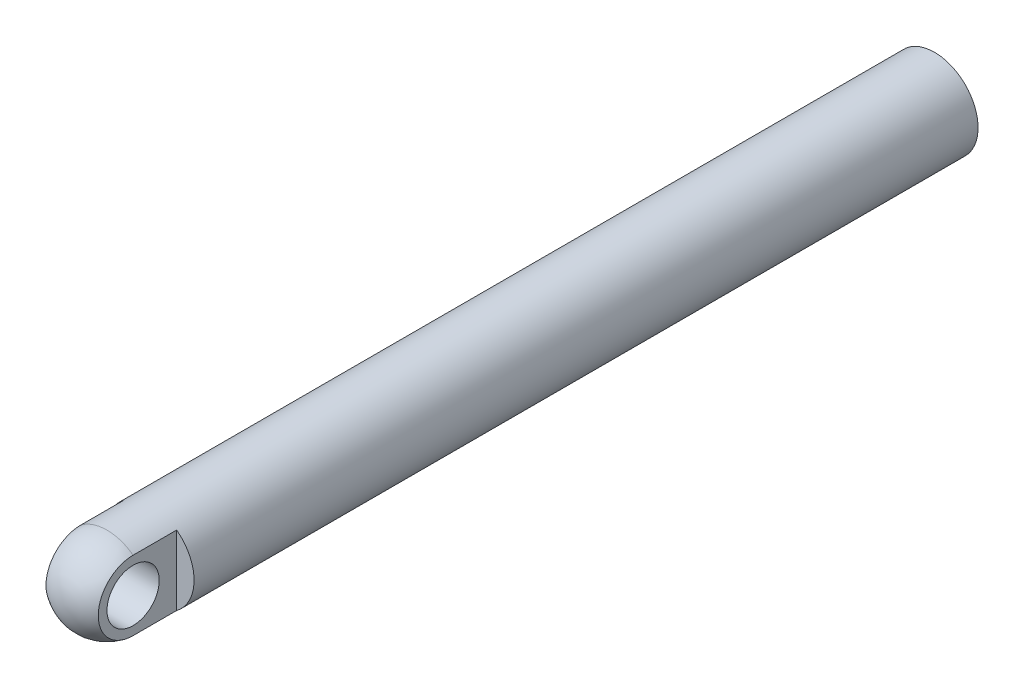
SolidWorks part; units mm, degrees
ref_plane "前视基准面" through (0, 0, 0) normal (0, 0, 1) x (1, 0, 0)
ref_plane "上视基准面" through (0, 0, 0) normal (0, 1, 0) x (1, 0, 0)
ref_plane "右视基准面" through (0, 0, 0) normal (1, 0, 0) x (0, 0, -1)
sketch "草图1" plane through (0, 0, 0) normal (0, 0, 1) x (1, 0, 0)
  circle A0 centre (0, 0) radius 50
extrude "凸台-拉伸1" add sketch "草图1" along normal blind 1150
sketch "草图2" plane through (0, 0, 1150) normal (0, 0, 1) x (1, 0, 0)
  line L1 (-30, 50) -> (-30, -50)
  line L2 (30, 50) -> (30, -50)
  line L3 (30, 50) -> (95.4457, 11.1353)
  line L4 (95.4457, 11.1353) -> (70.9724, -45.8873)
  line L5 (70.9724, -45.8873) -> (30, -50)
  line L6 (-30, -50) -> (-82.7196, -32.4271)
  line L7 (-82.7196, -32.4271) -> (-69.504, 45.1531)
  line L8 (-69.504, 45.1531) -> (-30, 50)
extrude "切除-拉伸1" cut sketch "草图2" against normal blind 100
sketch "草图3" plane through (30, 0, 0) normal (1, 0, 0) x (0, 0, -1)
  line L0 (-1050, 40) -> (-1050, -40) construction
  circle A0 centre (-1100, 0) radius 30
  dimension "D1" = 50
extrude "切除-拉伸2" cut sketch "草图3" against normal blind 100
fillet "圆角1" radius 50 1 edges at (0, 50, 1150)
sketch "草图4" plane through (0, 0, 0) normal (0, 0, -1) x (-1, 0, 0)
  circle A0 centre (0, 0) radius 50
extrude "切除-拉伸3" cut sketch "草图4" against normal blind 100
sketch "草图6" plane through (0, 0, 100) normal (0, 0, -1) x (-1, 0, 0)
  circle A0 centre (0, 0) radius 72.9064
extrude "切除-拉伸4" cut sketch "草图6" against normal blind 50
scale "缩放比例1" scale about origin uniform scaling yes scale factor 0.345
